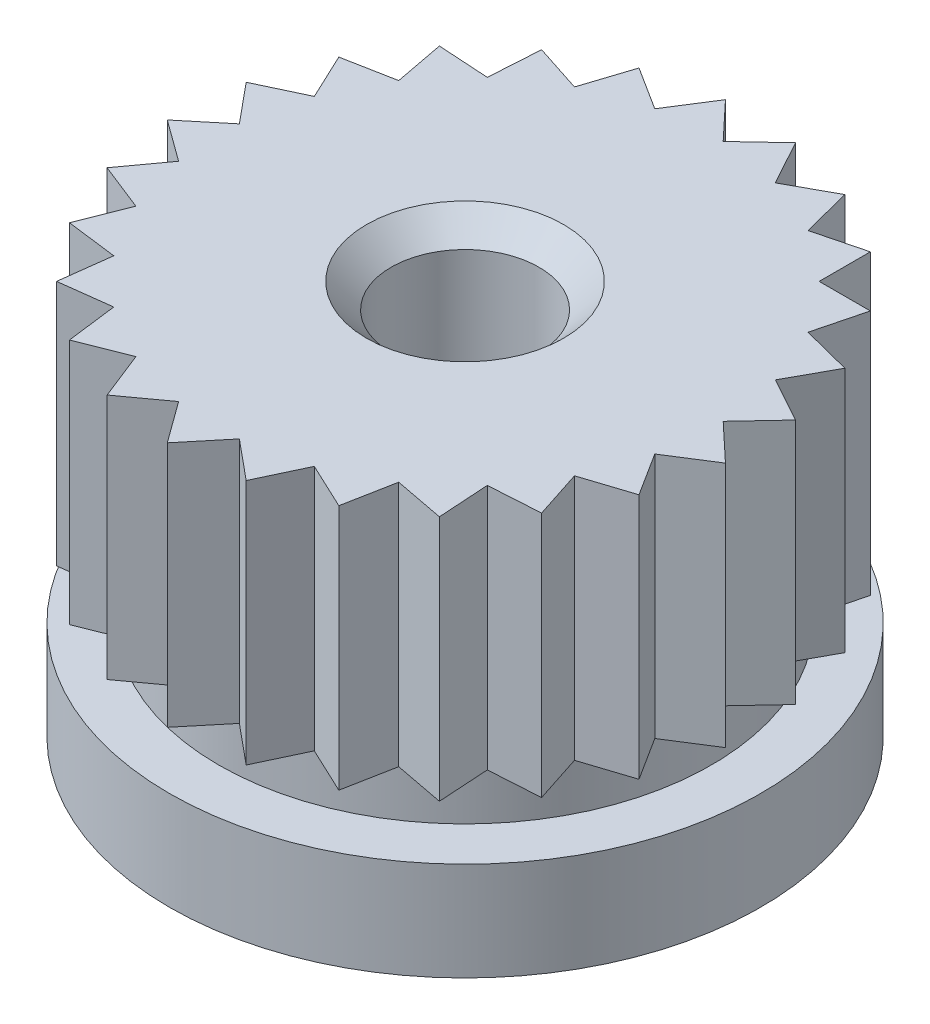
SolidWorks part; units mm, degrees
ref_plane "Front Plane" through (0, 0, 0) normal (0, 0, 1) x (1, 0, 0)
ref_plane "Top Plane" through (0, 0, 0) normal (0, 1, 0) x (1, 0, 0)
ref_plane "Right Plane" through (0, 0, 0) normal (1, 0, 0) x (0, 0, -1)
sketch "Sketch1" plane through (0, 0, 0) normal (0, 1, 0) x (1, 0, 0)
  circle A0 centre (0, 0) radius 3
  dimension "D1" = 6
extrude "Boss-Extrude1" add sketch "Sketch1" along normal blind 4
sketch "Sketch2" plane through (0, 4, 0) normal (0, 1, 0) x (1, 0, 0)
  line L0 (0, 0) -> (3, 0) construction
  line L1 (0, 0) -> (2.1213, 2.1213) construction
  line L3 (1.7963, 1.7963) -> (2.4463, 1.7963)
  line L4 (1.7963, 1.7963) -> (1.7963, 2.4463)
  line L5 (1.7963, 2.4463) -> (2.4463, 2.4463)
  line L6 (2.4463, 1.7963) -> (2.4463, 2.4463)
  line L7 (1.7963, 1.7963) -> (2.4463, 2.4463) construction
  line L8 (1.7963, 2.4463) -> (2.4463, 1.7963) construction
  circle A0 centre (0, 0) radius 3 construction
  dimension "D1" = 45
  dimension "D2" = 0.65
  dimension "D3" = 0.65
extrude "Cut-Extrude1" cut sketch "Sketch2" against normal blind 2.5
ref_axis "Axis1" through (0, 4, 0) along (0, -1, 0)
pattern_circular "CirPattern1" count 25 over 360 about axis through (0, 4, 0) along (0, -1, 0) of "Cut-Extrude1"
sketch "Sketch3" plane through (0, 1.5, 0) normal (0, 1, 0) x (1, 0, 0)
  circle A0 centre (0, 0) radius 2.5
  dimension "D1" = 5
extrude "Cut-Extrude2" cut sketch "Sketch3" against normal blind 0.5 flip side to cut
hole_wizard "CSK for M3 SFHCS1" positions "Sketch8" profile "Sketch7" countersink size "M3" standard "ANSI Metric" end condition through all
sketch "Sketch8" plane through (0, 4, 0) normal (0, 1, 0) x (1, 0, 0)
  point P1 (0, 0)
sketch "Sketch7" plane through (0, 4, 0) normal (1, 0, 0) x (0, 0, 1)
  line L0 (0, 0) -> (0, 4)
  line L1 (0, 4) -> (0.75, 4)
  line L2 (0.75, 4) -> (0.75, 0.25)
  line L3 (0.75, 0.25) -> (1, 0)
  line L5 (1, 0) -> (0, 0)
  line L6 (-0.75, 0.25) -> (-1, 0) construction
  line L11 (0, -6.35) -> (0, 107.95) construction
  dimension "Thru Hole Dia." = 1.5
  dimension "Thru Hole Depth" = 4
  dimension "Near C'Sink Dia." = 2
  dimension "Near C'Sink Angle" = 90
